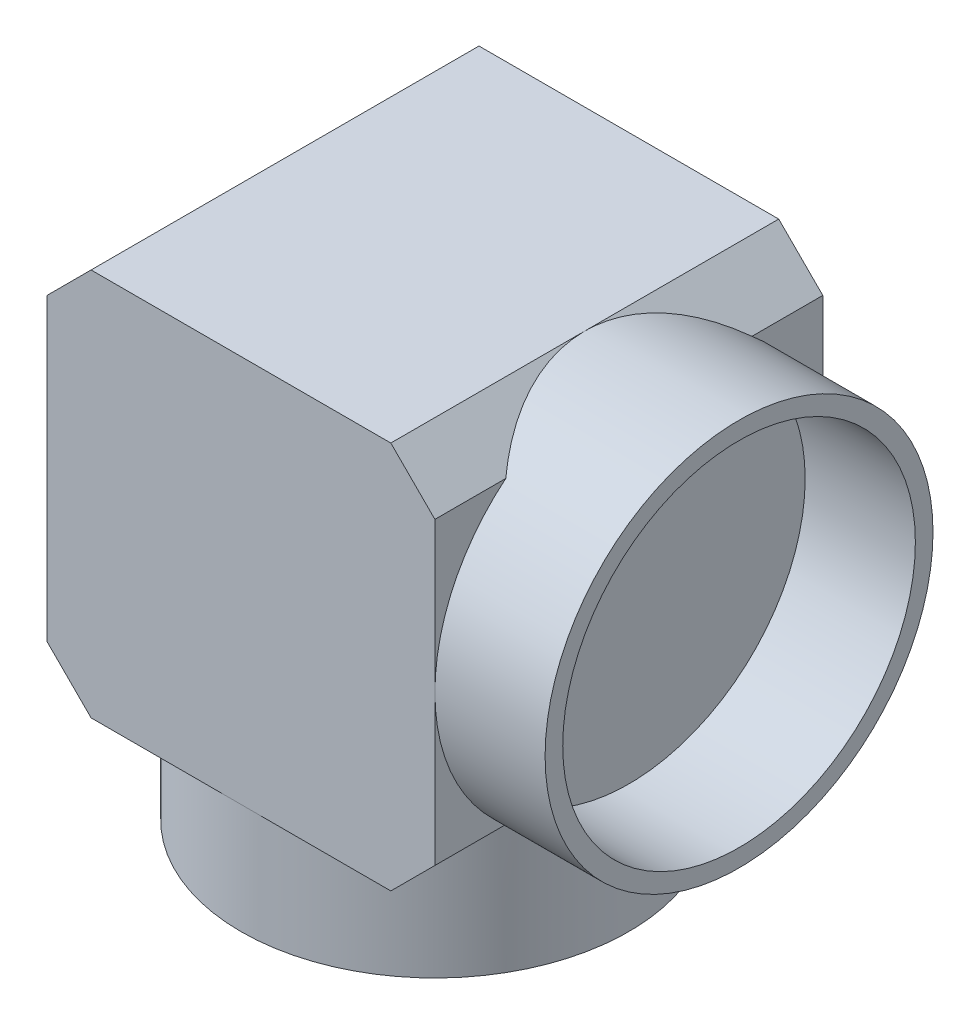
SolidWorks part; units mm, degrees
ref_plane "Front Plane" through (0, 0, 0) normal (0, 0, 1) x (1, 0, 0)
ref_plane "Top Plane" through (0, 0, 0) normal (0, 1, 0) x (1, 0, 0)
ref_plane "Right Plane" through (0, 0, 0) normal (1, 0, 0) x (0, 0, -1)
sketch "Sketch1" plane through (0, 0, 0) normal (0, 1, 0) x (1, 0, 0)
  line L0 (-40, 0) -> (40, 0) construction
  circle A0 centre (0, 0) radius 44
  circle A1 centre (0, 0) radius 40
  dimension "D1" = 80
  dimension "D2" = 4
extrude "Boss-Extrude1" add sketch "Sketch1" along normal blind 25
ref_plane "Plane1" through (44, 0, 0) normal (1, 0, 0) x (0, 0, -1)
sketch "Sketch2" plane through (44, 0, 0) normal (1, 0, 0) x (0, 0, -1)
  line L0 (0, 0) -> (0, 134.0371) construction
  line L2 (44, 25) -> (-44, 25) construction
  circle A0 centre (0, 69) radius 40
  circle A1 centre (0, 69) radius 44
  dimension "D1" = 80
  dimension "D2" = 4
extrude "Boss-Extrude2" add sketch "Sketch2" along normal blind 25 separate body
sketch "Sketch3" plane through (0, 25, 0) normal (0, 1, 0) x (1, 0, 0)
  line L1 (44, -44) -> (-44, -44)
  line L2 (44, -44) -> (44, 44)
  line L3 (44, 44) -> (-44, 44)
  line L4 (-44, -44) -> (-44, 44)
  line L5 (44, -44) -> (-44, 44) construction
  line L6 (44, 44) -> (-44, -44) construction
  circle A0 centre (0, 0) radius 44 construction
  point P0 (0, 0)
extrude "Boss-Extrude3" add sketch "Sketch3" along normal blind 88
chamfer "Chamfer2" distance 10 angle 45 7 edges at (-44, 113, 0) (44, 113, -22) (44, 113, 22) (-44, 25, 22) (-44, 25, -22) (44, 25, -22) (44, 25, 22)
